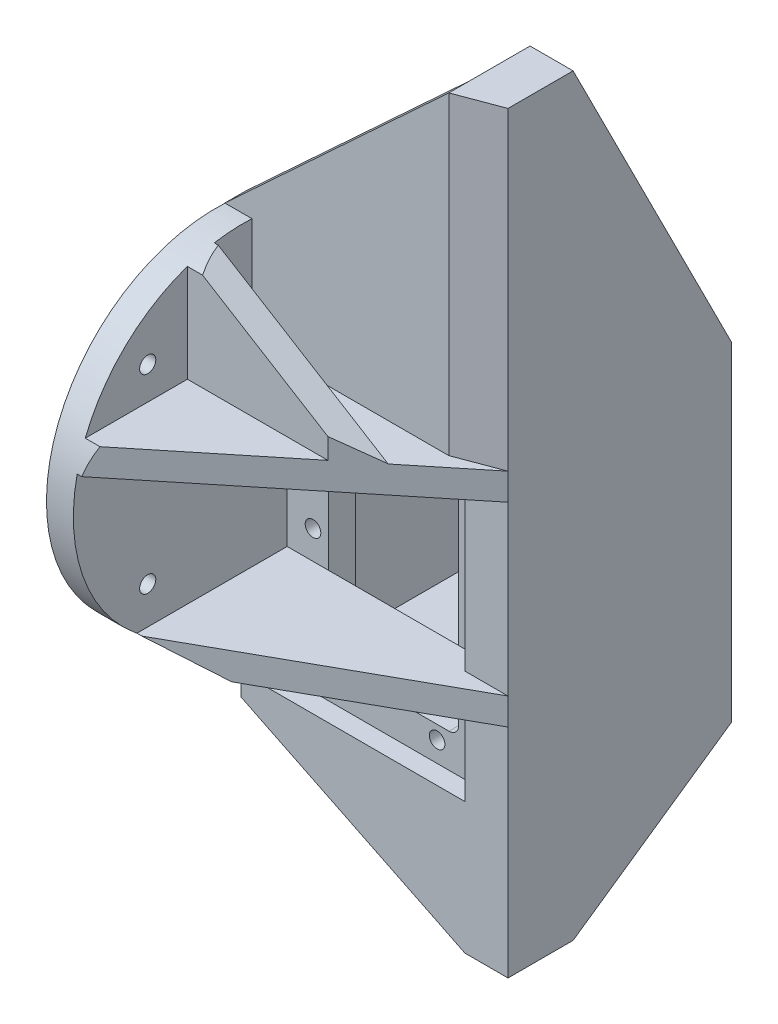
SolidWorks part; units mm, degrees
material "ABS"
ref_plane "Front Plane" through (0, 0, 0) normal (0, 0, 1) x (1, 0, 0)
ref_plane "Top Plane" through (0, 0, 0) normal (0, 1, 0) x (1, 0, 0)
ref_plane "Right Plane" through (0, 0, 0) normal (1, 0, 0) x (0, 0, -1)
sketch "Sketch1" plane through (0, 0, 0) normal (0, 0, 1) x (1, 0, 0)
  line L0 (-10.285, 45) -> (-11.785, 45)
  line L1 (-12.4921, 44.7071) -> (-17.5063, 39.6929)
  line L2 (-17.7992, 38.9858) -> (-17.7992, 0.4142)
  line L3 (-17.5063, -0.2929) -> (-12.4921, -5.3071)
  line L4 (-11.785, -5.6) -> (11.7866, -5.6)
  line L5 (12.4937, -5.3071) -> (17.5079, -0.2929)
  line L6 (17.8008, 0.4142) -> (17.8008, 38.9858)
  line L7 (17.5079, 39.6929) -> (12.4937, 44.7071)
  line L8 (11.7866, 45) -> (10.285, 45)
  line L9 (11.785, 43.5) -> (11.785, 1.5)
  line L10 (10.285, 0) -> (-10.285, 0)
  line L11 (-11.785, 1.5) -> (-11.785, 43.5)
  line L12 (-10.285, 45) -> (10.285, 45)
  line L13 (24.8008, 56.1927) -> (24.8008, -14.4857)
  line L14 (-24.7992, 61.4878) -> (-24.7992, -15.9821)
  line L15 (-24.7992, 50.6) -> (24.8008, 50.6)
  line L16 (-11.785, -5.6) -> (-24.7992, -5.6)
  line L17 (11.7866, -5.6) -> (24.8008, -5.6)
  line L18 (-12.085, 1.5) -> (-12.085, 43.5)
  line L19 (10.285, -0.3) -> (-10.285, -0.3)
  line L20 (12.085, 43.5) -> (12.085, 1.5)
  line L21 (-10.285, 45.3) -> (10.285, 45.3)
  circle A0 centre (-14.9992, 36.7) radius 1.35
  circle A1 centre (-14.9992, 19.7) radius 1.35
  circle A2 centre (-14.9992, 2.7) radius 1.35
  circle A3 centre (-7.6975, -2.8) radius 1.35
  arc A4 (-10.285, 45) -> (-11.785, 43.5) centre (-10.285, 43.5) ccw
  arc A5 (-11.785, 45) -> (-12.4921, 44.7071) centre (-11.785, 44) ccw
  arc A6 (-17.5063, 39.6929) -> (-17.7992, 38.9858) centre (-16.7992, 38.9858) ccw
  arc A7 (-17.7992, 0.4142) -> (-17.5063, -0.2929) centre (-16.7992, 0.4142) ccw
  arc A8 (-12.4921, -5.3071) -> (-11.785, -5.6) centre (-11.785, -4.6) ccw
  arc A9 (11.7866, -5.6) -> (12.4937, -5.3071) centre (11.7866, -4.6) ccw
  arc A10 (17.5079, -0.2929) -> (17.8008, 0.4142) centre (16.8008, 0.4142) ccw
  arc A11 (17.8008, 38.9858) -> (17.5079, 39.6929) centre (16.8008, 38.9858) ccw
  arc A12 (12.4937, 44.7071) -> (11.7866, 45) centre (11.7866, 44) ccw
  arc A13 (11.785, 43.5) -> (10.285, 45) centre (10.285, 43.5) ccw
  arc A14 (10.285, 0) -> (11.785, 1.5) centre (10.285, 1.5) ccw
  arc A15 (-11.785, 1.5) -> (-10.285, 0) centre (-10.285, 1.5) ccw
  circle A16 centre (8.0763, -2.8) radius 1.35
  circle A17 centre (15.0008, 2.7) radius 1.35
  circle A18 centre (15.0008, 19.7) radius 1.35
  circle A19 centre (15.0008, 36.7) radius 1.35
  circle A20 centre (-14.9992, 36.7) radius 1.45
  circle A21 centre (-14.9992, 19.7) radius 1.45
  circle A22 centre (-14.9992, 2.7) radius 1.45
  circle A23 centre (-7.6975, -2.8) radius 1.45
  circle A24 centre (8.0763, -2.8) radius 1.45
  circle A25 centre (15.0008, 2.7) radius 1.45
  circle A26 centre (15.0008, 19.7) radius 1.45
  circle A27 centre (15.0008, 36.7) radius 1.45
  arc A28 (-10.285, 45.3) -> (-12.085, 43.5) centre (-10.285, 43.5) ccw
  arc A29 (-12.085, 1.5) -> (-10.285, -0.3) centre (-10.285, 1.5) ccw
  arc A30 (10.285, -0.3) -> (12.085, 1.5) centre (10.285, 1.5) ccw
  arc A31 (12.085, 43.5) -> (10.285, 45.3) centre (10.285, 43.5) ccw
  dimension "D2" = 7
  dimension "D3" = 7
  dimension "D4" = 5.6
  dimension "D5" = 0.3
  dimension "D1" = 0.1
extrude "Boss-Extrude1" add sketch "Sketch1" along normal blind 3 contours A31 L8 A12 L7 A11 L6 A10 L5 A9 L17 L13 L15 L14 L16 A8 L3 A7 L2 A6 L1 A5 L0 A28 L21 | A31 L20 A30 L19 A29 L18 A28 L0 A5 L1 A6 L2 A7 L3 A8 L4 A9 L5 A10 L6 A11 L7 A12 L8 A27 A26 A25 A24 A23 A22 A21 A20 region at (-12.4162, 44.6437, 0) region at (-11.5325, 45.7496, 0)
extrude "Boss-Extrude2" add sketch "Sketch1<3>" against normal blind 3 from offset 30 separate body contours A31 L8 A12 L7 A11 L6 A10 L5 A9 L17 L13 L15 L14 L16 A8 L3 A7 L2 A6 L1 A5 L0 A28 L21 | A31 L20 A30 L19 A29 L18 A28 L0 A5 L1 A6 L2 A7 L3 A8 L4 A9 L5 A10 L6 A11 L7 A12 L8 A27 A26 A25 A24 A23 A22 A21 A20 region at (-12.4162, 44.6437, 0) region at (-11.5325, 45.7496, 0) offset against normal yes
sketch "Sketch1<3>" plane through (0, 0, 0) normal (0, 0, 1) x (1, 0, 0) same geometry as "Sketch1"
sketch "Sketch2" plane through (0, 0, 3) normal (0, 0, 1) x (1, 0, 0)
  line L0 (-12.085, 43.5) -> (-12.085, 56.6919)
  line L1 (-12.085, 56.6919) -> (12.085, 56.6919)
  line L2 (12.085, 56.6919) -> (12.085, 43.5)
  line L3 (-12.085, 43.5) -> (12.085, 43.5)
extrude "Cut-Extrude1" cut sketch "Sketch2" against normal through all
sketch "Sketch3" plane through (0, 0, -33) normal (0, 0, -1) x (-1, 0, 0)
  line L0 (-19.8008, 50.6) -> (-19.8008, -5.6)
  line L1 (-12.085, 50.6) -> (-24.8008, 50.6) construction
  line L2 (24.7992, -5.6) -> (-24.8008, -5.6) construction
  line L3 (-24.8008, 50.6) -> (-24.8008, -5.6) construction
  line L4 (19.7992, 50.6) -> (19.7992, -5.6)
  line L5 (24.7992, 50.6) -> (12.085, 50.6) construction
  line L6 (24.7992, 50.6) -> (24.7992, -5.6) construction
  line L15 (24.7992, 50.6) -> (12.085, 50.6)
  line L16 (12.085, 50.6) -> (12.085, 1.5)
  line L17 (10.285, -0.3) -> (-10.285, -0.3)
  line L18 (-12.085, 1.5) -> (-12.085, 50.6)
  line L19 (-12.085, 50.6) -> (-24.8008, 50.6)
  line L20 (-24.8008, 50.6) -> (-24.8008, -5.6)
  line L21 (-24.8008, -5.6) -> (24.7992, -5.6)
  line L22 (24.7992, -5.6) -> (24.7992, 50.6)
  line L23 (24.7992, 50.6) -> (12.085, 50.6)
  line L24 (12.085, 50.6) -> (12.085, 1.5)
  line L25 (10.285, -0.3) -> (-10.285, -0.3)
  line L26 (-12.085, 1.5) -> (-12.085, 50.6)
  line L27 (-12.085, 50.6) -> (-24.8008, 50.6)
  line L28 (-24.8008, 50.6) -> (-24.8008, -5.6)
  line L29 (-24.8008, -5.6) -> (24.7992, -5.6)
  line L30 (24.7992, -5.6) -> (24.7992, 50.6)
  arc A2 (10.285, -0.3) -> (12.085, 1.5) centre (10.285, 1.5) ccw
  arc A3 (-12.085, 1.5) -> (-10.285, -0.3) centre (-10.285, 1.5) ccw
  arc A4 (10.285, -0.3) -> (12.085, 1.5) centre (10.285, 1.5) ccw
  arc A5 (-12.085, 1.5) -> (-10.285, -0.3) centre (-10.285, 1.5) ccw
  line M13 (24.7992, 50.6) -> (12.085, 50.6)
  line M19 (-12.085, 50.6) -> (-24.8008, 50.6)
  line M20 (-24.8008, 50.6) -> (-24.8008, -5.6)
  line M21 (-24.8008, -5.6) -> (24.7992, -5.6)
  line M22 (24.7992, -5.6) -> (24.7992, 50.6)
  dimension "D1" = 5
  dimension "D2" = 5
  dimension "D3" = 0
extrude "Boss-Extrude3" add sketch "Sketch3" against normal up to surface (33 mm away) contours L0 M19 M20 M21 | L4 M13 M21 M22 region at (22.3008, 22.5, -33) region at (-22.2992, 22.5, -33) up to face at (0.0003, 19.2854, 0)
sketch "Sketch4" plane through (0, 0, -33) normal (0, 0, -1) x (-1, 0, 0)
  line L0 (-24.8008, -5.6) -> (-24.8008, -10.6)
  line L1 (-24.8008, -10.6) -> (24.7992, -10.6)
  line L2 (24.7992, -10.6) -> (24.7992, -5.6)
  line L3 (-24.8008, -5.6) -> (24.7992, -5.6) construction
  line L4 (-24.8008, -5.6) -> (24.7992, -5.6)
  dimension "D1" = 5
extrude "Boss-Extrude4" add sketch "Sketch4" against normal up to surface (36 mm away) up to face at (0.0003, 19.2854, 3)
sketch "Sketch6" plane through (-24.7992, 0, 0) normal (-1, 0, 0) x (0, 0, 1)
  circle A0 centre (13.25, 39) radius 31.5
  dimension "D3" = 63
  dimension "D1" = 11.6
  dimension "D2" = 10.25
extrude "Boss-Extrude6" add sketch "Sketch6" against normal up to surface (5 mm away) up to face at (-19.7992, 22.5, -15)
hole_wizard "Ø6.0mm Clearance Dowel Hole1" positions "Sketch7" profile "Sketch8" hole size "Ø6.0" standard "ISO"
sketch "Sketch7" plane through (-24.7992, 0, 0) normal (-1, 0, 0) x (0, 0, 1)
  line L0 (13.25, 39) -> (-16.6201, 68.8701)
  line L2 (13.25, 39) -> (13.25, 84.7316)
  line L4 (13.25, 39) -> (38.4679, 13.7821)
  line L6 (13.25, 39) -> (-19.6868, 6.0632)
  line L8 (13.25, 39) -> (49.2698, 75.0198)
  circle A0 centre (13.25, 39) radius 25
  point P29 (-4.4277, 21.3223)
  point P31 (-4.4277, 56.6777)
  point P33 (30.9277, 56.6777)
  point P35 (30.9277, 21.3223)
  dimension "D1" = 50
  dimension "D2" = 45
sketch "Sketch8" plane through (-24.7992, 21.3223, 30.9277) normal (0, 1, 0) x (0, 0, 1)
  line L0 (0, 0) -> (0, 20.9013)
  line L1 (0, 20.9013) -> (1.5, 20)
  line L2 (1.5, 20) -> (1.5, 0)
  line L5 (1.5, 0) -> (0, 0)
  line L10 (0, 20.9013) -> (-1.5, 20) construction
  line L11 (0, -6.35) -> (0, 107.95) construction
  dimension "Hole Dia." = 3
  dimension "Hole Depth" = 20
  dimension "Drill Angle" = 118
sketch "Sketch9" plane through (-24.7992, 0, 0) normal (-1, 0, 0) x (0, 0, 1)
  line L0 (3, -10.6) -> (33.4414, 14.8223)
  line L1 (-33, 50.6) -> (-1.1814, 66.9997)
  line L4 (-16.0363, 50.6) -> (-33, 50.6)
  line L5 (-33, 50.6) -> (-33, -10.6)
  line L6 (-33, -10.6) -> (3, -10.6)
  line L7 (3, -10.6) -> (3, 9.2143)
  line L8 (-16.0363, 50.6) -> (-33, 50.6)
  line L9 (-33, 50.6) -> (-33, -10.6)
  line L10 (-33, -10.6) -> (3, -10.6)
  line L11 (3, -10.6) -> (3, 9.2143)
  arc A1 (3, 9.2143) -> (-16.0363, 50.6) centre (13.25, 39) ccw
  arc A2 (3, 9.2143) -> (-16.0363, 50.6) centre (13.25, 39) ccw
  arc M10 (3, 9.2143) -> (-16.0363, 50.6) centre (13.25, 39) ccw
  line M11 (-16.0363, 50.6) -> (-33, 50.6)
  line M14 (3, -10.6) -> (3, 9.2143)
  dimension "D1" = 0
extrude "Boss-Extrude7" add sketch "Sketch9" against normal up to surface (5 mm away) contours L0 M14 M10 | L1 M11 M10 region at (-24.7992, 2.1505, 11.0392) region at (-24.7992, 55.1741, -18.7931) up to face at (-19.7992, 22.8223, -4.4277)
sketch "Sketch11" plane through (24.8008, 0, 0) normal (1, 0, 0) x (0, 0, -1)
  line L0 (-13.25, 39) -> (46.2081, 39)
  line L1 (-8.55, 109) -> (-8.55, -31)
  line L2 (-3, 50.6) -> (-3, -10.6) construction
  line L3 (3.55, 109) -> (3.55, -31)
  line L4 (-8.55, -31) -> (3.55, -31)
  line L5 (-8.55, 109) -> (3.55, 109)
  arc A0 (1.1814, 66.9997) -> (-33.4414, 14.8223) centre (-13.25, 39) ccw construction
  arc A1 (1.1814, 66.9997) -> (-33.4414, 14.8223) centre (-13.25, 39) ccw
  point P8 (-8.55, 39)
  point P10 (3.55, -21.8955)
  point P13 (3.55, 39)
  line M7 (-3, 50.6) -> (-3, -10.6)
  line M8 (-3, -10.6) -> (33, -10.6)
  line M10 (33, 50.6) -> (-3, 50.6)
  dimension "D1" = 5.55
  dimension "D2" = 12.1
  dimension "D3" = 70
extrude "Boss-Extrude8" add sketch "Sketch11" against normal blind 8 contours L3 L0 M7 M8 | L1 L4 L3 L0 M8 M7 | L5 L1 L0 L3 M7 M10 | L3 L0 M10 M7 region at (24.8008, 76.8775, 2.7735) region at (24.8008, -2.3468, 4.2267) region at (24.8008, 44.8, -0.275) region at (24.8008, 14.2, -0.275)
sketch "Sketch12" plane through (0, 0, 3) normal (0, 0, 1) x (1, 0, 0)
  line L8 (-19.7992, -10.6) -> (16.8008, -10.6)
  line L9 (16.8008, -10.6) -> (16.8008, 50.6)
  line L10 (16.8008, 50.6) -> (12.085, 50.6)
  line L11 (12.085, 50.6) -> (12.085, 1.5)
  line L12 (10.285, -0.3) -> (-10.285, -0.3)
  line L13 (-12.085, 1.5) -> (-12.085, 50.6)
  line L14 (-12.085, 50.6) -> (-19.7992, 50.6)
  line L15 (-19.7992, 50.6) -> (-19.7992, -10.6)
  line L16 (-19.7992, -10.6) -> (16.8008, -10.6)
  line L17 (16.8008, -10.6) -> (16.8008, 50.6)
  line L18 (16.8008, 50.6) -> (12.085, 50.6)
  line L19 (12.085, 50.6) -> (12.085, 1.5)
  line L20 (10.285, -0.3) -> (-10.285, -0.3)
  line L21 (-12.085, 1.5) -> (-12.085, 50.6)
  line L22 (-12.085, 50.6) -> (-19.7992, 50.6)
  line L23 (-19.7992, 50.6) -> (-19.7992, -10.6)
  circle A0 centre (-14.9992, 36.7) radius 1.45 construction
  circle A1 centre (-14.9992, 36.7) radius 1.45
  arc A2 (10.285, -0.3) -> (12.085, 1.5) centre (10.285, 1.5) ccw
  arc A3 (-12.085, 1.5) -> (-10.285, -0.3) centre (-10.285, 1.5) ccw
  arc A4 (10.285, -0.3) -> (12.085, 1.5) centre (10.285, 1.5) ccw
  arc A5 (-12.085, 1.5) -> (-10.285, -0.3) centre (-10.285, 1.5) ccw
  circle A6 centre (15.0008, 36.7) radius 1.45 construction
  circle A7 centre (15.0008, 19.7) radius 1.45 construction
  circle A8 centre (15.0008, 2.7) radius 1.45 construction
  circle A9 centre (8.0763, -2.8) radius 1.45 construction
  circle A10 centre (-7.6975, -2.8) radius 1.45 construction
  circle A11 centre (-14.9992, 2.7) radius 1.45 construction
  circle A12 centre (-14.9992, 19.7) radius 1.45 construction
  circle A13 centre (15.0008, 36.7) radius 1.45
  circle A14 centre (15.0008, 19.7) radius 1.45
  circle A15 centre (15.0008, 2.7) radius 1.45
  circle A16 centre (8.0763, -2.8) radius 1.45
  circle A17 centre (-7.6975, -2.8) radius 1.45
  circle A18 centre (-14.9992, 2.7) radius 1.45
  circle A19 centre (-14.9992, 19.7) radius 1.45
  dimension "D1" = 0
extrude "Boss-Extrude9" add sketch "Sketch12" along normal blind 2
sketch "Sketch14" plane through (0, 0, 5) normal (0, 0, 1) x (1, 0, 0)
  line L0 (24.8008, 109) -> (24.8008, -31) construction
  line L1 (24.8008, 109) -> (24.8008, -31)
  line L2 (-19.7992, 12.935) -> (24.8008, 12.935)
  line L3 (-19.7992, 50.6) -> (-19.7992, -8.9297) construction
  line L4 (-19.7992, -10.6) -> (24.8008, -10.6)
  line L5 (-19.7992, -10.6) -> (-19.7992, 12.935)
  line L6 (-19.7992, -10.6) -> (-24.7992, -10.6) construction
  line L7 (-19.7992, -10.6) -> (-24.7992, -10.6)
  line L8 (-24.7992, -10.6) -> (-24.7992, 12.935)
  line L9 (-24.7992, 12.935) -> (-19.7992, 12.935)
  circle A0 centre (15.0008, 2.7) radius 1.45 construction
  circle A1 centre (8.0763, -2.8) radius 1.45 construction
  circle A2 centre (-7.6975, -2.8) radius 1.45 construction
  circle A3 centre (-14.9992, 2.7) radius 1.45 construction
  circle A4 centre (15.0008, 2.7) radius 1.45
  circle A5 centre (8.0763, -2.8) radius 1.45
  circle A6 centre (-7.6975, -2.8) radius 1.45
  circle A7 centre (-14.9992, 2.7) radius 1.45
  circle M1 centre (-14.9992, 2.7) radius 1.45
  circle M2 centre (8.0763, -2.8) radius 1.45
  line M5 (-19.7992, 50.6) -> (-19.7992, -8.9297)
  line M6 (-19.7992, -8.9297) -> (-19.7992, -10.6)
  line M7 (-19.7992, -10.6) -> (16.8008, -10.6)
  line M8 (16.8008, -10.6) -> (16.8008, 50.6)
  line M10 (12.085, 50.6) -> (12.085, 1.5)
  arc M11 (12.085, 1.5) -> (10.285, -0.3) centre (10.285, 1.5) cw
  line M12 (10.285, -0.3) -> (-10.285, -0.3)
  arc M13 (-10.285, -0.3) -> (-12.085, 1.5) centre (-10.285, 1.5) cw
  line M14 (-12.085, 1.5) -> (-12.085, 50.6)
  circle M17 centre (15.0008, 2.7) radius 1.45
  circle M18 centre (-7.6975, -2.8) radius 1.45
extrude "Boss-Extrude11" [suppressed] add sketch "Sketch14" against normal blind 1 and the other way blind 7 contours L2 M5 M6 M7 M8 M10 M11 M12 M13 M14 M2 M18 M17 M1 | L2 M14 M13 M12 M11 M10 | L4 L1 L2 M8
sketch "Sketch15" plane through (0, 50.6, 0) normal (0, 1, 0) x (1, 0, 0)
  line L2 (-19.7992, -44.75) -> (-19.7992, 1.1814) construction
  line L3 (-19.7992, -44.75) -> (-19.7992, 1.1814)
  line L4 (12.085, 0) -> (12.085, -5)
  line L5 (12.085, -5) -> (16.8008, -5)
  line L6 (16.8008, -5) -> (16.8008, 0)
  line L7 (16.8008, 0) -> (12.085, 0)
  line L8 (12.085, 0) -> (12.085, -5)
  line L9 (12.085, -5) -> (16.8008, -5)
  line L10 (16.8008, -5) -> (16.8008, 0)
  line L11 (16.8008, 0) -> (12.085, 0)
  line L12 (-19.7992, -44.75) -> (24.8008, -8.55)
  line L14 (12.085, -5) -> (-19.7992, -5)
  line L15 (16.8008, -5) -> (24.8008, -5)
  line L16 (24.8008, -5) -> (24.8008, -8.55)
  line M6 (12.085, -5) -> (16.8008, -5)
  dimension "D1" = 0
extrude "Boss-Extrude12" add sketch "Sketch15" against normal blind 5 contours L14 L3 M6 region at (-3.7137, 50.6, 18.347)
ref_plane "Plane1" through (0, 14.4, 0) normal (0, -1, 0) x (-1, 0, 0)
sketch "Sketch16" plane through (0, 14.4, 0) normal (0, -1, 0) x (-1, 0, 0)
  line L0 (19.7992, -33.4414) -> (19.7992, -44.75) construction
  line L1 (19.7992, -33.4414) -> (19.7992, -44.75)
  line L2 (19.7992, -5) -> (-16.8008, -5) construction
  line L3 (19.7992, -5) -> (-16.8008, -5)
  line L4 (19.7992, -33.4414) -> (19.7992, -5)
  line L5 (-16.8008, -8.55) -> (-24.8008, -8.55) construction
  line L6 (-16.8008, -8.55) -> (-24.8008, -8.55)
  line L7 (-24.8008, -8.55) -> (19.7992, -33.4414)
  line L8 (-16.8008, -5) -> (-24.8008, -5)
  line L9 (-24.8008, -5) -> (-24.8008, -8.55)
extrude "Boss-Extrude13" add sketch "Sketch16" along normal blind 5 contours L8 L9 L7 L4 L3 region at (-3.2828, 14.4, 14.6118)
ref_plane "Plane2" through (0, 0, 18.55) normal (0, 0, 1) x (1, 0, 0)
sketch "Sketch17" plane through (0, 0, 18.55) normal (0, 0, 1) x (1, 0, 0)
  line L2 (-19.7992, 50.6) -> (-19.7992, 70.5) construction
  line L3 (-19.7992, 50.6) -> (-19.7992, 70.5)
  line L4 (12.5543, 50.6) -> (-19.7992, 50.6)
  line L5 (12.5543, 50.6) -> (-19.7992, 70.5)
extrude "Boss-Extrude14" add sketch "Sketch17" along normal blind 5
sketch "Sketch18" plane through (-24.7992, 0, 0) normal (-1, 0, 0) x (0, 0, 1)
  line L0 (3, -10.6) -> (3, 68.7857)
  line L1 (3, -10.6) -> (3, -33.7261)
  line L2 (3, -33.7261) -> (83.736, -32.2894)
  line L3 (83.736, -32.2894) -> (81.7759, 77.8617)
  line L4 (-33, -10.6) -> (3, -10.6)
  line L5 (3, -10.6) -> (33.4414, 14.8223)
  line L6 (-1.1814, 66.9997) -> (-33, 50.6)
  line L7 (-33, 50.6) -> (-33, -10.6)
  line L8 (-33, -10.6) -> (3, -10.6)
  line L9 (3, -10.6) -> (33.4414, 14.8223)
  line L10 (-1.1814, 66.9997) -> (-33, 50.6)
  line L11 (-33, 50.6) -> (-33, -10.6)
  line L12 (81.7759, 77.8617) -> (3, 77.8617)
  line L13 (3, 77.8617) -> (3, 68.7857)
  arc A0 (33.4414, 14.8223) -> (-1.1814, 66.9997) centre (13.25, 39) ccw construction
  arc A1 (33.4414, 14.8223) -> (-1.1814, 66.9997) centre (13.25, 39) ccw
  arc A3 (33.4414, 14.8223) -> (-1.1814, 66.9997) centre (13.25, 39) ccw
  arc A4 (33.4414, 14.8223) -> (-1.1814, 66.9997) centre (13.25, 39) ccw
  line M7 (3, -10.6) -> (33.4414, 14.8223)
  arc M8 (33.4414, 14.8223) -> (-1.1814, 66.9997) centre (13.25, 39) ccw
  dimension "D1" = 0
extrude "Cut-Extrude3" cut sketch "Sketch18" against normal up to surface (41.6 mm away) contours L12 L13 L1 L2 L3 M8 M7 region at (-24.7992, 17.146, 51.1952) up to face at (16.8008, 30, 6.775)
sketch "Sketch19" plane through (0, 45.6, 0) normal (0, -1, 0) x (1, 0, 0)
  line L0 (-18.9378, 44.0508) -> (-12.085, 55.6996)
  line L1 (-12.085, 55.6996) -> (42.1076, 23.8189)
  line L2 (42.1076, 23.8189) -> (24.8008, 8.55)
  line L8 (-18.9378, 44.0508) -> (-19.7992, 44.0508)
  line L9 (-19.7992, 44.0508) -> (-19.7992, 5)
  line L10 (-19.7992, 5) -> (-12.085, 5)
  line L11 (-12.085, 5) -> (12.085, 5)
  line L12 (12.085, 5) -> (16.8008, 5)
  line L13 (16.8008, 5) -> (16.8008, 8.55)
  line L14 (16.8008, 8.55) -> (24.8008, 8.55)
  line L15 (24.8008, 8.55) -> (-18.9378, 44.0508)
  line L16 (-18.9378, 44.0508) -> (-19.7992, 44.0508)
  line L17 (-19.7992, 44.0508) -> (-19.7992, 5)
  line L18 (-19.7992, 5) -> (-12.085, 5)
  line L19 (-12.085, 5) -> (12.085, 5)
  line L20 (12.085, 5) -> (16.8008, 5)
  line L21 (16.8008, 5) -> (16.8008, 8.55)
  line L22 (16.8008, 8.55) -> (24.8008, 8.55)
  line L23 (24.8008, 8.55) -> (-18.9378, 44.0508)
  line M16 (24.8008, 8.55) -> (-18.9378, 44.0508)
  dimension "D1" = 0
extrude "Cut-Extrude4" cut sketch "Sketch19" against normal blind 20 contours L2 L1 L0 M16 region at (11.0897, 45.6, 31.7374)
sketch "Sketch20" plane through (0, 0, 8.55) normal (0, 0, 1) x (1, 0, 0)
  line L0 (-24.7992, -10.6) -> (-24.7992, 14.8223) construction
  line L1 (-24.7992, -10.6) -> (-24.7992, 14.8223)
  line L2 (16.8008, -10.6) -> (-24.7992, -10.6) construction
  line L3 (16.8008, -10.6) -> (-24.7992, -10.6)
  line L4 (24.8008, 9.4) -> (16.8008, 9.4)
  line L5 (16.8008, 9.4) -> (16.8008, -31)
  line L6 (16.8008, -31) -> (24.8008, -31)
  line L7 (24.8008, -31) -> (24.8008, 9.4)
  line L8 (24.8008, 9.4) -> (16.8008, 9.4)
  line L9 (16.8008, 9.4) -> (16.8008, -31)
  line L10 (16.8008, -31) -> (24.8008, -31)
  line L11 (24.8008, -31) -> (24.8008, 9.4)
  line L12 (16.8008, -31) -> (-24.7992, -10.6)
  line L13 (16.8008, -6.6) -> (-19.7992, -6.6)
  line L14 (-19.7992, -8.9297) -> (-19.7992, 9.4) construction
  line L15 (-19.7992, -6.6) -> (-19.7992, 9.4)
  line L16 (-19.7992, 9.4) -> (-24.7992, 9.4)
  line M8 (16.8008, 9.4) -> (16.8008, -31)
  dimension "D2" = 4
  dimension "D1" = 0
extrude "Boss-Extrude15" add sketch "Sketch20" against normal up to surface (12.1 mm away) contours L12 L3 M8 | L9 L13 L1 L3 region at (-24.3376, -0.6, 8.55) region at (2.9341, -17.4, 8.55) up to face at (20.8008, -20.8, -3.55)
sketch "Sketch21" plane through (0, 0, 8.55) normal (0, 0, 1) x (1, 0, 0)
  line L0 (-24.7992, 70.5) -> (-24.7992, 14.8223) construction
  line L1 (-24.7992, 70.5) -> (-24.7992, 14.8223)
  line L2 (-24.7992, 70.5) -> (16.8008, 109)
  line L3 (16.8008, 50.6) -> (-24.7992, 50.6)
  line L4 (16.8008, 50.6) -> (24.8008, 50.6)
  line L5 (24.8008, 50.6) -> (24.8008, 109)
  line L6 (24.8008, 109) -> (16.8008, 109)
  line L7 (16.8008, 109) -> (16.8008, 50.6)
  line L8 (16.8008, 50.6) -> (24.8008, 50.6)
  line L9 (24.8008, 50.6) -> (24.8008, 109)
  line L10 (24.8008, 109) -> (16.8008, 109)
  line L11 (16.8008, 109) -> (16.8008, 50.6)
  line M8 (16.8008, 109) -> (16.8008, 50.6)
  dimension "D1" = 0
extrude "Boss-Extrude18" add sketch "Sketch21" against normal blind 0.8 and the other way blind 3 contours L3 L2 L1 M8 region at (-0.5901, 71.7525, 8.55)
sketch "Sketch22" plane through (0, 109, 0) normal (0, 1, 0) x (1, 0, 0)
  line L0 (-19.7992, 0) -> (-12.085, 0) construction
  line L1 (12.085, 0) -> (16.8008, 0) construction
  line L2 (-19.7992, 0) -> (-12.085, 0)
  line L3 (12.085, 0) -> (16.8008, 0)
  line L4 (3.5, -7.75) -> (-3.5, -7.75)
  line L5 (12.085, 0) -> (-12.085, 0)
  line L6 (3.5, -7.75) -> (3.5, 0)
  line L7 (-3.5, -7.75) -> (-3.5, 0)
  point P6 (0, 0)
  dimension "D1" = 7.75
  dimension "D2" = 7
  dimension "D3" = 3.5
extrude "Cut-Extrude6" cut sketch "Sketch22" against normal blind 70 and the other way through all contours L7 L4 L6 L5 region at (0, 109, 3.875)
sketch "Sketch23" plane through (0, 109, 0) normal (0, 1, 0) x (1, 0, 0)
  line L0 (24.8008, -8.55) -> (16.8008, -11.55)
  line L1 (16.8008, -11.55) -> (16.8008, -8.55)
  line L5 (24.8008, -8.55) -> (24.8008, 3.55)
  line L6 (24.8008, 3.55) -> (16.8008, 3.55)
  line L7 (16.8008, 3.55) -> (16.8008, -7.75)
  line L8 (16.8008, -7.75) -> (16.8008, -8.55)
  line L9 (16.8008, -8.55) -> (24.8008, -8.55)
  line L10 (24.8008, -8.55) -> (24.8008, 3.55)
  line L11 (24.8008, 3.55) -> (16.8008, 3.55)
  line L12 (16.8008, 3.55) -> (16.8008, -7.75)
  line L13 (16.8008, -7.75) -> (16.8008, -8.55)
  line L14 (16.8008, -8.55) -> (24.8008, -8.55)
  line M10 (16.8008, -8.55) -> (24.8008, -8.55)
  dimension "D1" = 0
extrude "Boss-Extrude19" add sketch "Sketch23" against normal up to surface (58.4 mm away) contours L1 L0 M10 region at (19.4675, 109, 9.55) up to face at (5.214, 50.6, 12.8833)
sketch "Sketch24" plane through (24.8008, 0, 0) normal (1, 0, 0) x (0, 0, -1)
  line L0 (33, -10.6) -> (3.55, -31)
  line L1 (33, 50.6) -> (3.55, 109)
  line L12 (-8.55, 14.4) -> (-8.55, 9.4)
  line L13 (-8.55, 9.4) -> (-8.55, -31)
  line L14 (-8.55, -31) -> (3.55, -31)
  line L15 (3.55, -31) -> (3.55, -10.6)
  line L16 (3.55, -10.6) -> (33, -10.6)
  line L17 (33, -10.6) -> (33, 50.6)
  line L18 (33, 50.6) -> (3.55, 50.6)
  line L19 (3.55, 50.6) -> (3.55, 109)
  line L20 (3.55, 109) -> (-8.55, 109)
  line L21 (-8.55, 109) -> (-8.55, 50.6)
  line L22 (-8.55, 50.6) -> (-8.55, 45.6)
  line L23 (-8.55, 45.6) -> (-8.55, 14.4)
  line L24 (-8.55, 14.4) -> (-8.55, 9.4)
  line L25 (-8.55, 9.4) -> (-8.55, -31)
  line L26 (-8.55, -31) -> (3.55, -31)
  line L27 (3.55, -31) -> (3.55, -10.6)
  line L28 (3.55, -10.6) -> (33, -10.6)
  line L29 (33, -10.6) -> (33, 50.6)
  line L30 (33, 50.6) -> (3.55, 50.6)
  line L31 (3.55, 50.6) -> (3.55, 109)
  line L32 (3.55, 109) -> (-8.55, 109)
  line L33 (-8.55, 109) -> (-8.55, 50.6)
  line L34 (-8.55, 50.6) -> (-8.55, 45.6)
  line L35 (-8.55, 45.6) -> (-8.55, 14.4)
  line M16 (3.55, -31) -> (3.55, -10.6)
  line M17 (3.55, -10.6) -> (33, -10.6)
  line M19 (33, 50.6) -> (3.55, 50.6)
  line M20 (3.55, 50.6) -> (3.55, 109)
  dimension "D1" = 0
extrude "Boss-Extrude20" add sketch "Sketch24" against normal blind 5 contours L0 M17 M16 | L1 M19 M20 region at (24.8008, -17.4, -13.3667) region at (24.8008, 70.0667, -13.3667)
